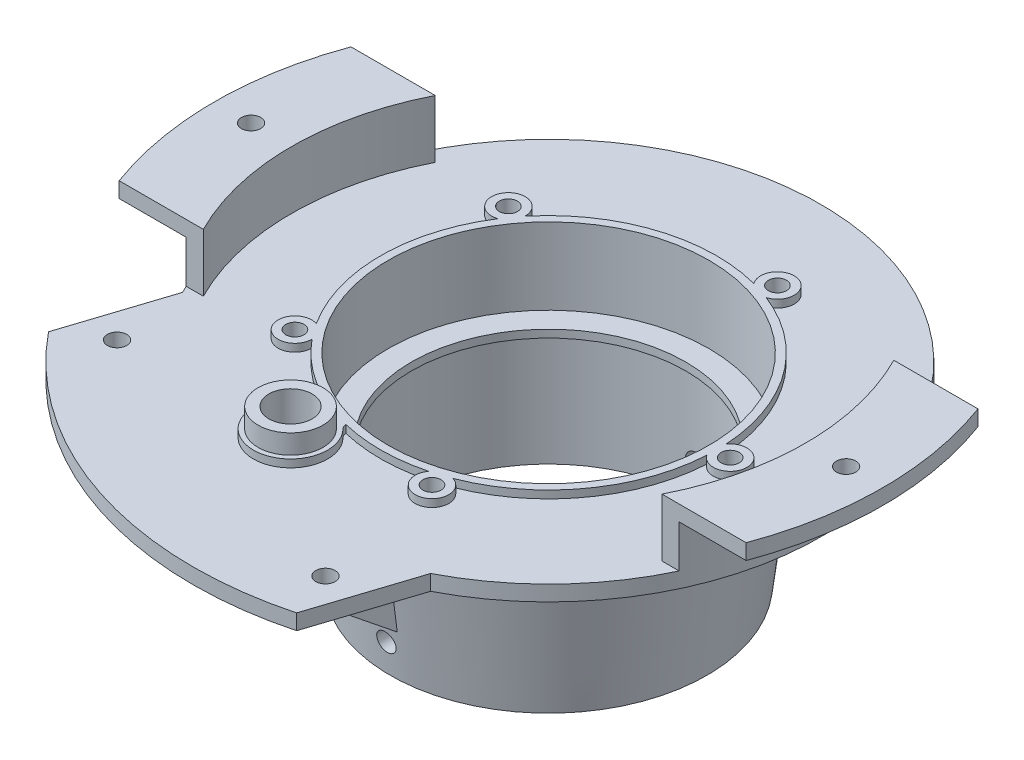
SolidWorks part; units mm, degrees
ref_plane "Front Plane" through (0, 0, 0) normal (0, 0, 1) x (1, 0, 0)
ref_plane "Top Plane" through (0, 0, 0) normal (0, 1, 0) x (1, 0, 0)
ref_plane "Right Plane" through (0, 0, 0) normal (1, 0, 0) x (0, 0, -1)
sketch "Sketch1" plane through (0, 0, 0) normal (0, 0, 1) x (1, 0, 0)
  line L26 (-70.5, -4) -> (-70.5, 11)
  line L27 (-70.5, 11) -> (-86.5, 11)
  line L28 (-86.5, 11) -> (-86.5, 15)
  line L29 (-86.5, 15) -> (-66.5, 15)
  line L30 (-66.5, 15) -> (-66.5, 0)
  line L31 (-66.5, 0) -> (-41.5, 0)
  line L36 (-38, -19.8) -> (-38, -49.8)
  line L37 (-38, -49.8) -> (-41, -49.8)
  line L38 (-37.5, -17.8) -> (-35.5, -17.8)
  line L41 (-37.5, -17.8) -> (-41.5, -17.8)
  line L42 (-41.5, 0) -> (-41.5, -17.8)
  line L43 (-35.5, -17.8) -> (-35.5, -19.8)
  line L44 (-35.5, -19.8) -> (-38, -19.8)
  line L45 (-70.5, -4) -> (-56.5, -4)
  line L47 (-45.5, -15) -> (-41, -49.8)
  line L48 (-56.5, -4) -> (-45.5, -15)
  dimension "D2" = 4
  dimension "D3" = 35.5
  dimension "D4" = 41.5
  dimension "D5" = 17.8
  dimension "D6" = 2
  dimension "D7" = 15
  dimension "D8" = 4
  dimension "D9" = 38
  dimension "D10" = 3
  dimension "D11" = 20
  dimension "D12" = 4
  dimension "D13" = 4
  dimension "D14" = 30
  dimension "D15" = 4
  dimension "D16" = 25
  dimension "D17" = 15
  dimension "D18" = 15
ref_axis "Axis1" through (0, -100.5, 0) along (0, 1, 0)
revolve "Revolve1" add sketch "Sketch1" angle 360 about axis through (0, -100.5, 0) along (0, 1, 0)
sketch "Sketch2" plane through (0, 11, 0) normal (0, -1, 0) x (1, 0, 0)
  circle A0 centre (77, 0) radius 2.5
  circle A1 centre (-77, 0) radius 2.5
  dimension "D1" = 5
  dimension "D3" = 77
  dimension "D2" = 77
extrude "Cut-Extrude3" cut sketch "Sketch2" against normal up to surface (4 mm away) up to face at (0, 15, -86.5)
sketch "Sketch3" plane through (0, 15, 0) normal (0, 1, 0) x (1, 0, 0)
  line L0 (-59.3485, -30) -> (-81.1311, -30)
  line L1 (81.1311, -30) -> (59.3485, -30)
  line L5 (81.1311, 30) -> (59.3485, 30)
  line L9 (-59.3485, 30) -> (-81.1311, 30)
  circle A0 centre (0, 0) radius 86.5 construction
  circle A1 centre (-77, 0) radius 2.5 construction
  arc A2 (-81.1311, -30) -> (81.1311, -30) centre (0, 0) ccw
  circle A3 centre (0, 0) radius 66.5 construction
  arc A4 (-59.3485, -30) -> (59.3485, -30) centre (0, 0) ccw
  arc A5 (59.3485, 30) -> (-59.3485, 30) centre (0, 0) ccw
  arc A6 (81.1311, 30) -> (-81.1311, 30) centre (0, 0) ccw
  dimension "D2" = 30
  dimension "D1" = 30
extrude "Cut-Extrude4" cut sketch "Sketch3" against normal up to surface (15 mm away) up to face at (0, 0, -66.5)
sketch "Sketch6" plane through (0, 0, 0) normal (0, 0, 1) x (1, 0, 0)
  line L0 (0, -100.5) -> (0, 20.5) construction
  line L2 (-41, -49.8) -> (41, -49.8) construction
  circle A0 centre (0, -41.8) radius 2.5
  dimension "D1" = 5
  dimension "D2" = 8
extrude "Cut-Extrude6" cut sketch "Sketch6" against normal through all both and the other way through all
sketch "Sketch7" plane through (0, 0, 0) normal (0, 1, 0) x (1, 0, 0)
  circle A0 centre (47, 0) radius 2.35
  dimension "D1" = 4.7
  dimension "D2" = 47
extrude "Cut-Extrude7" cut sketch "Sketch7" against normal up to surface (13.4413 mm away) contours A0 up to face at (0, -15, -45.5)
pattern_circular "CirPattern1" count 5 every 72 about axis through (0, -100.5, 0) along (0, 1, 0) of "Cut-Extrude7"
sketch "Sketch9" plane through (0, 0, 0) normal (0, 1, 0) x (1, 0, 0)
  circle A0 centre (-16.377, -50.4063) radius 5.6
  circle A3 centre (-38.0238, -27.6259) radius 2.35 construction
  circle A4 centre (14.5238, -44.6997) radius 2.35 construction
  dimension "D1" = 11.2
  dimension "D3" = 31.425
  dimension "D2" = 53
  dimension "D4" = 31.4233
extrude "Cut-Extrude8" cut sketch "Sketch9" against normal through all contours A0
sketch "Sketch8" plane through (0, 0, 0) normal (0, 1, 0) x (1, 0, 0)
  circle A0 centre (0, 0) radius 41.5 construction
  circle A1 centre (0, 0) radius 41.5
  arc A2 (-33.6747, -27.5366) -> (-17.3102, -39.9075) centre (0, 0) ccw
  circle A3 centre (-38.0238, -27.6259) radius 2.35 construction
  circle A4 centre (14.5238, -44.6997) radius 2.35 construction
  circle A5 centre (47, 0) radius 2.35 construction
  circle A6 centre (14.5238, 44.6997) radius 2.35 construction
  circle A7 centre (-38.0238, 27.6259) radius 2.35 construction
  circle A8 centre (-38.0238, -27.6259) radius 2.35
  circle A9 centre (14.5238, -44.6997) radius 2.35
  circle A10 centre (47, 0) radius 2.35
  circle A11 centre (14.5238, 44.6997) radius 2.35
  circle A12 centre (-38.0238, 27.6259) radius 2.35
  arc A13 (-33.6747, 27.5366) -> (-36.5949, 23.5173) centre (-38.0238, 27.6259) ccw
  arc A14 (15.7828, 40.5358) -> (11.0578, 42.0711) centre (14.5238, 44.6997) ccw
  arc A15 (43.429, -2.4841) -> (43.429, 2.4841) centre (47, 0) ccw
  arc A16 (11.0578, -42.0711) -> (15.7828, -40.5358) centre (14.5238, -44.6997) ccw
  arc A17 (-36.5949, -23.5173) -> (-33.6747, -27.5366) centre (-38.0238, -27.6259) ccw
  arc A18 (15.7828, -40.5358) -> (43.429, -2.4841) centre (0, 0) ccw
  circle A19 centre (-38.0238, -27.6259) radius 4.35 construction
  circle A20 centre (0, 0) radius 43.5 construction
  circle A21 centre (14.5238, -44.6997) radius 4.35 construction
  arc A22 (43.429, 2.4841) -> (15.7828, 40.5358) centre (0, 0) ccw
  arc A23 (11.0578, 42.0711) -> (-33.6747, 27.5366) centre (0, 0) ccw
  circle A24 centre (47, 0) radius 4.35 construction
  arc A25 (-36.5949, 23.5173) -> (-36.5949, -23.5173) centre (0, 0) ccw
  circle A26 centre (14.5238, 44.6997) radius 4.35 construction
  circle A27 centre (-38.0238, 27.6259) radius 4.35 construction
  circle A28 centre (-16.377, -50.4063) radius 5.6 construction
  circle A29 centre (-16.377, -50.4063) radius 5.6
  arc A30 (-19.3485, -41.2778) -> (-9.394, -43.8186) centre (-16.377, -50.4063) ccw
  arc A31 (-17.3102, -39.9075) -> (-19.3485, -41.2778) centre (-19.5582, -38.7645) cw
  arc A32 (-10.1543, -42.2982) -> (-9.394, -43.8186) centre (-8.0531, -42.1977) ccw
  arc A33 (-10.1543, -42.2982) -> (11.0578, -42.0711) centre (0, 0) ccw
  circle A34 centre (-16.377, -50.4063) radius 9.6 construction
  point P4 (18.6238, -44.6997)
  point P23 (-33.9238, 27.6259)
  point P29 (41.5993, 12.7182)
  point P30 (-33.9238, -27.6259)
  point P39 (51.1, 0)
  point P42 (18.6238, 44.6997)
  point P57 (-8.777, -50.4063)
  dimension "D1" = 2
  dimension "D2" = 2
  dimension "D3" = 4
extrude "Boss-Extrude1" add sketch "Sketch8" along normal blind 2
sketch "Sketch10" plane through (0, 2, 0) normal (0, 1, 0) x (1, 0, 0)
  circle A0 centre (-16.377, -50.4063) radius 5.6 construction
  circle A1 centre (-16.377, -50.4063) radius 5.6
  circle A2 centre (-16.377, -50.4063) radius 8.4
  dimension "D1" = 2.8
extrude "Boss-Extrude2" add sketch "Sketch10" along normal blind 5
ref_point "Point1"
sketch "Sketch15" plane through (0, 0, 0) normal (0, 1, 0) x (1, 0, 0)
  line L0 (0, 0) -> (-16.377, -50.4063)
  line L1 (-16.377, -50.4063) -> (-33.367, -102.6994)
sketch "Sketch11" plane through (0, 0, 0) normal (0, 1, 0) x (1, 0, 0)
  line L0 (-62.9109, -31.8193) -> (-71.4162, -57.9976)
  line L1 (32.1953, -62.7193) -> (23.69, -88.8976)
  line L3 (-16.377, -50.4063) -> (-33.367, -102.6994) construction
  arc A0 (-63.7985, -30) -> (63.7985, -30) centre (0, 0) ccw construction
  arc A1 (-62.9109, -31.8193) -> (32.1953, -62.7193) centre (0, 0) ccw
  arc A4 (23.69, -88.8976) -> (-71.4162, -57.9976) centre (0, 0) cw
  point P3 (0, 0)
  point P4 (-86.4221, -40.6383)
  point P5 (86.4221, -40.6383)
  point P11 (-21.7845, -67.0499)
  point P14 (-28.428, -87.4977)
  dimension "D2" = 21.5
  dimension "D1" = 100
extrude "Boss-Extrude3" add sketch "Sketch11" against normal up to surface (4 mm away) up to face at (-0.3244, -4, 0.9986)
ref_axis "Axis2" through (23.69, 0, 88.8976) along (-0.9511, 0, -0.309)
sketch "Sketch16" plane through (0, 0, 0) normal (0, 1, 0) x (1, 0, 0)
  line L0 (23.69, -88.8976) -> (32.1953, -62.7193) construction
  line L1 (-62.9109, -31.8193) -> (-71.4162, -57.9976) construction
  line L2 (23.69, -88.8976) -> (-71.4162, -57.9976) construction
  circle A0 centre (19.1715, -76.915) radius 2.5
  circle A1 centre (-60.7177, -50.959) radius 2.5
  dimension "D3" = 5
  dimension "D4" = 10
  dimension "D5" = 10
  dimension "D1" = 8
  dimension "D2" = 8
extrude "Cut-Extrude9" cut sketch "Sketch16" against normal up to surface (4 mm away) up to face at (-0.3244, -4, 0.9986)
sketch "Sketch17" plane through (0, 0, 0) normal (0, 1, 0) x (1, 0, 0)
  line L0 (0, 0) -> (-55.406, -73.4451)
  line L1 (0, 0) -> (1.6578, -91.9851)
  line L2 (-55.406, -73.4451) -> (1.6578, -91.9851)
  line L3 (0, 0) -> (-16.377, -50.4063)
  line L4 (-16.377, -50.4063) -> (-33.0404, -101.6941)
  arc A0 (-71.4162, -57.9976) -> (23.69, -88.8976) centre (0, 0) ccw construction
  point P10 (-26.8741, -82.7151)
  dimension "D1" = 60
ref_plane "Plane2" through (0, 0, 0) normal (-0.7983, 0, -0.6022) x (-0.6022, 0, 0.7983)
ref_plane "Plane3" through (0, 0, 0) normal (-0.9998, 0, 0.018) x (0.018, 0, 0.9998)
sketch "Sketch18" plane through (0, 0, 0) normal (-0.7983, 0, -0.6022) x (-0.6022, 0, 0.7983)
  line L2 (89.31, -4) -> (63.2893, -4) construction
  line L27 (27.5163, -15) -> (45.5, -15) construction
  line L29 (44.8194, -15) -> (42.0003, -38.1306)
  line L30 (42.0003, -38.1306) -> (84.2847, -4)
  line L31 (44.8194, -15) -> (55.4437, -4)
  line L32 (-56.5, -4) -> (56.5, -4) construction
  line L33 (55.4437, -4) -> (84.2847, -4)
extrude "Boss-Extrude8" add sketch "Sketch18" along normal mid plane 5
ref_plane "Plane4" through (0, 0, 0) normal (0.9511, 0, 0.309) x (0.309, 0, -0.9511)
mirror "Mirror1" about plane through (0, 0, 0) normal (0.9511, 0, 0.309) of "Boss-Extrude8"
